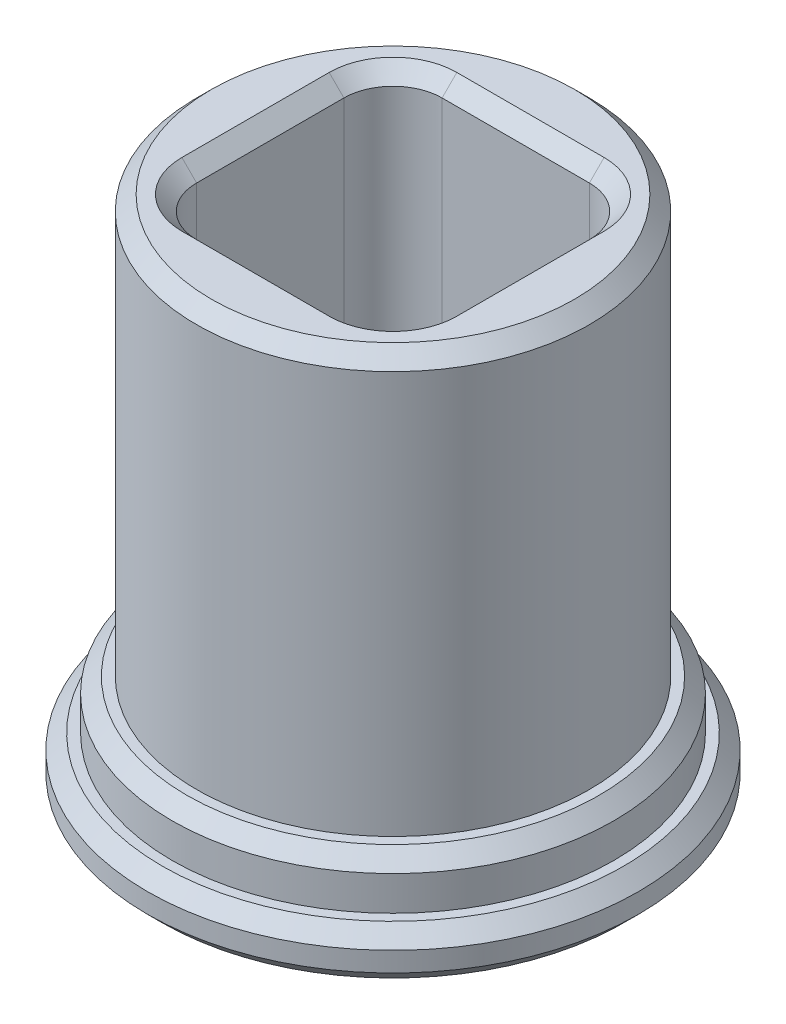
SolidWorks part; units mm, degrees
material "보통 탄소강"
ref_plane "정면" through (0, 0, 0) normal (0, 0, 1) x (1, 0, 0)
ref_plane "윗면" through (0, 0, 0) normal (0, 1, 0) x (1, 0, 0)
ref_plane "우측면" through (0, 0, 0) normal (1, 0, 0) x (0, 0, -1)
sketch "스케치1" plane through (0, 0, 0) normal (0, 1, 0) x (1, 0, 0)
  line L1 (-2.5, -2.5) -> (2.5, -2.5)
  line L2 (-2.5, -2.5) -> (-2.5, 2.5)
  line L3 (-2.5, 2.5) -> (2.5, 2.5)
  line L4 (2.5, -2.5) -> (2.5, 2.5)
  line L5 (-2.5, -2.5) -> (2.5, 2.5) construction
  line L6 (-2.5, 2.5) -> (2.5, -2.5) construction
  circle A0 centre (0, 0) radius 4
  circle A1 centre (0, 0) radius 5
  circle A2 centre (0, 0) radius 4.5
  dimension "D1" = 8
  dimension "D2" = 10
  dimension "D3" = 9
  dimension "D4" = 5
extrude "보스-돌출1" add sketch "스케치1" along normal blind 1 contours A1 A2 region at (-4.8586, 0, 0)
extrude "보스-돌출2" add sketch "스케치1<5>" along normal blind 2 contours A2 A0 region at (-4.3727, 0, 0)
sketch "스케치1<5>" plane through (0, 0, 0) normal (0, 1, 0) x (1, 0, 0) same geometry as "스케치1"
extrude "보스-돌출3" add sketch "스케치1<6>" along normal blind 10.5 contours A0 L4 L1 L2 L3 | L1 L4 L3 L2 region at (0, 0, 0) region at (-3.8869, 0, 0)
sketch "스케치1<6>" plane through (0, 0, 0) normal (0, 1, 0) x (1, 0, 0) same geometry as "스케치1"
extrude "컷-돌출1" cut sketch "스케치1<7>" against normal blind 6 from surface contours L1 L4 L3 L2 region at (0, 0, 0) starting at face at (0, 10.5, 4)
sketch "스케치1<7>" plane through (0, 0, 0) normal (0, 1, 0) x (1, 0, 0) same geometry as "스케치1"
sketch "스케치2" plane through (0, 0, 0) normal (0, -1, 0) x (1, 0, 0)
  circle A0 centre (0, 0) radius 2.2
  dimension "D1" = 4.4
extrude "컷-돌출2" cut sketch "스케치2" against normal blind 20
sketch "스케치3" plane through (0, 0, 0) normal (0, -1, 0) x (1, 0, 0)
  circle A0 centre (0, 0) radius 3.75
  dimension "D1" = 7.5
extrude "컷-돌출4" cut sketch "스케치3" against normal blind 1
fillet "필렛1" radius 1 4 edges at (2.5, 7.5, 2.5) (-2.5, 7.5, 2.5) (2.5, 7.5, -2.5) (-2.5, 7.5, -2.5)
chamfer "모따기1" distance 0.3 angle 45 14 edges at (0, 0, -3.75) (0, 1, -2.2) (0, 0, 5) (0, 1, 5) (0, 2, 4.5) (2.2071, 10.5, -2.2071) (2.5, 10.5, 0) (2.2071, 10.5, 2.2071) (0, 10.5, 2.5) (-2.2071, 10.5, 2.2071) (0, 10.5, -2.5) (-2.2071, 10.5, -2.2071) (-2.5, 10.5, 0) (0, 10.5, 4)
